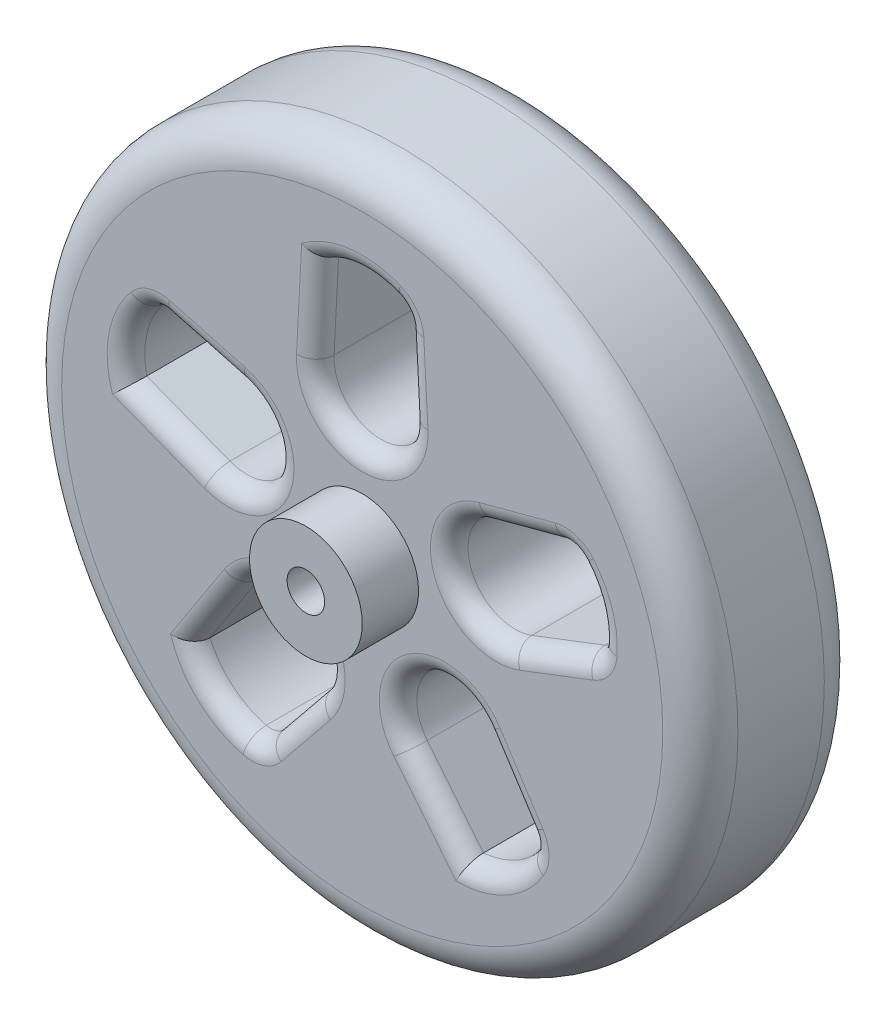
SolidWorks part; units mm, degrees
ref_plane "Front Plane" through (0, 0, 0) normal (0, 0, 1) x (1, 0, 0)
ref_plane "Top Plane" through (0, 0, 0) normal (0, 1, 0) x (1, 0, 0)
ref_plane "Right Plane" through (0, 0, 0) normal (1, 0, 0) x (0, 0, -1)
sketch "Sketch1" plane through (0, 0, 0) normal (0, 0, 1) x (1, 0, 0)
  circle A0 centre (0, 0) radius 90
  circle A1 centre (0, 0) radius 70
  dimension "D1" = 180
  dimension "D2" = 20
extrude "Boss-Extrude1" add sketch "Sketch1" along normal mid plane 43
fillet "Fillet2" radius 10 2 edges at (90, 0, -21.5) (90, 0, 21.5)
sketch "Sketch2" plane through (0, 0, 0) normal (0, 0, 1) x (1, 0, 0)
  line L0 (0, 0) -> (0, 65) construction
  line L1 (11.2564, 61.9022) -> (12.5, 38.1723)
  line L2 (-11.2564, 61.9022) -> (-12.5, 38.1723)
  line L3 (55.3941, 29.8343) -> (32.4413, 23.6841)
  line L4 (62.3509, 8.4234) -> (40.1667, -0.0923)
  line L5 (45.4918, -43.4636) -> (32.5498, -23.5347)
  line L6 (27.2786, -56.6963) -> (12.3244, -38.2293)
  line L7 (-27.2786, -56.6963) -> (-12.3244, -38.2293)
  line L8 (-45.4918, -43.4636) -> (-32.5498, -23.5347)
  line L9 (-62.3509, 8.4234) -> (-40.1667, -0.0923)
  line L10 (-55.3941, 29.8343) -> (-32.4413, 23.6841)
  circle A0 centre (0, 0) radius 10
  circle A1 centre (0, 0) radius 70
  circle A2 centre (0, 0) radius 70 construction
  arc A4 (0, 65) -> (11.2564, 61.9022) centre (0, 43) cw
  arc A5 (12.5, 38.1723) -> (0, 25) centre (0, 37.5172) cw
  arc A6 (-12.5, 38.1723) -> (0, 25) centre (0, 37.5172) ccw
  arc A7 (0, 65) -> (-11.2564, 61.9022) centre (0, 43) ccw
  arc A8 (32.4413, 23.6841) -> (23.7764, 7.7254) centre (35.6809, 11.5934) ccw
  arc A9 (61.8187, 20.0861) -> (55.3941, 29.8343) centre (40.8954, 13.2877) ccw
  arc A10 (61.8187, 20.0861) -> (62.3509, 8.4234) centre (40.8954, 13.2877) cw
  arc A11 (40.1667, -0.0923) -> (23.7764, 7.7254) centre (35.6809, 11.5934) cw
  arc A12 (32.5498, -23.5347) -> (14.6946, -20.2254) centre (22.052, -30.352) ccw
  arc A13 (38.206, -52.5861) -> (45.4918, -43.4636) centre (25.2748, -34.7877) ccw
  arc A14 (38.206, -52.5861) -> (27.2786, -56.6963) centre (25.2748, -34.7877) cw
  arc A15 (12.3244, -38.2293) -> (14.6946, -20.2254) centre (22.052, -30.352) cw
  arc A16 (-12.3244, -38.2293) -> (-14.6946, -20.2254) centre (-22.052, -30.352) ccw
  arc A17 (-38.206, -52.5861) -> (-27.2786, -56.6963) centre (-25.2748, -34.7877) ccw
  arc A18 (-38.206, -52.5861) -> (-45.4918, -43.4636) centre (-25.2748, -34.7877) cw
  arc A19 (-32.5498, -23.5347) -> (-14.6946, -20.2254) centre (-22.052, -30.352) cw
  arc A20 (-40.1667, -0.0923) -> (-23.7764, 7.7254) centre (-35.6809, 11.5934) ccw
  arc A21 (-61.8187, 20.0861) -> (-62.3509, 8.4234) centre (-40.8954, 13.2877) ccw
  arc A22 (-61.8187, 20.0861) -> (-55.3941, 29.8343) centre (-40.8954, 13.2877) cw
  arc A23 (-32.4413, 23.6841) -> (-23.7764, 7.7254) centre (-35.6809, 11.5934) cw
  point P16 (-50.3409, 19.688)
  point P17 (0, 0)
  point P53 (0, 0)
  dimension "D1" = 20
  dimension "D6" = 22
  dimension "D2" = 65
  dimension "D3" = 40
  dimension "D4" = 25
  dimension "D5" = 3
  dimension "D7" = 5
extrude "Boss-Extrude3" add sketch "Sketch2" along normal up to surface and the other way up to surface separate body up to face at (80, 0, 21.5) other way up to face at (80, 0, -21.5)
fillet "Fillet1" radius 5 46 edges at (23.7764, 7.7254, -21.5) (23.7764, 7.7254, 21.5) (0, 65, -21.5) (0, 65, 21.5) (-38.206, -52.5861, -21.5) (-38.206, -52.5861, 21.5) (38.206, -52.5861, -21.5) (38.206, -52.5861, 21.5) (-61.8187, 20.0861, -21.5) (-61.8187, 20.0861, 21.5) (43.9177, 26.7592, -21.5) (51.2588, 4.1655, -21.5) (43.9177, 26.7592, 21.5) (51.2588, 4.1655, 21.5) (-11.8782, 50.0372, -21.5) (0, 25, -21.5) (-11.8782, 50.0372, 21.5) (0, 25, 21.5) (-39.0208, -33.4992, -21.5) (-14.6946, -20.2254, -21.5) (-39.0208, -33.4992, 21.5) (-14.6946, -20.2254, 21.5) (19.8015, -47.4628, -21.5) (14.6946, -20.2254, -21.5) (19.8015, -47.4628, 21.5) (14.6946, -20.2254, 21.5) (-51.2588, 4.1655, -21.5) (-23.7764, 7.7254, -21.5) (-51.2588, 4.1655, 21.5) (-23.7764, 7.7254, 21.5) (11.8782, 50.0372, -21.5) (11.2564, 61.9022, 0) (11.8782, 50.0372, 21.5) (-19.8015, -47.4628, -21.5) (-19.8015, -47.4628, 21.5) (-27.2786, -56.6963, 0) (39.0208, -33.4992, -21.5) (39.0208, -33.4992, 21.5) (45.4918, -43.4636, 0) (-43.9177, 26.7592, -21.5) (-55.3941, 29.8343, 0) (-43.9177, 26.7592, 21.5) (61.8187, 20.0861, -21.5) (55.3941, 29.8343, 0) (61.8187, 20.0861, 21.5) (62.3509, 8.4234, 0)
sketch "Sketch3" plane through (0, 0, 21.5) normal (0, 0, 1) x (1, 0, 0)
  circle A0 centre (0, 0) radius 15
  circle A1 centre (0, 0) radius 5
  dimension "D1" = 10
  dimension "D2" = 30
extrude "Boss-Extrude4" add sketch "Sketch3" along normal blind 15
